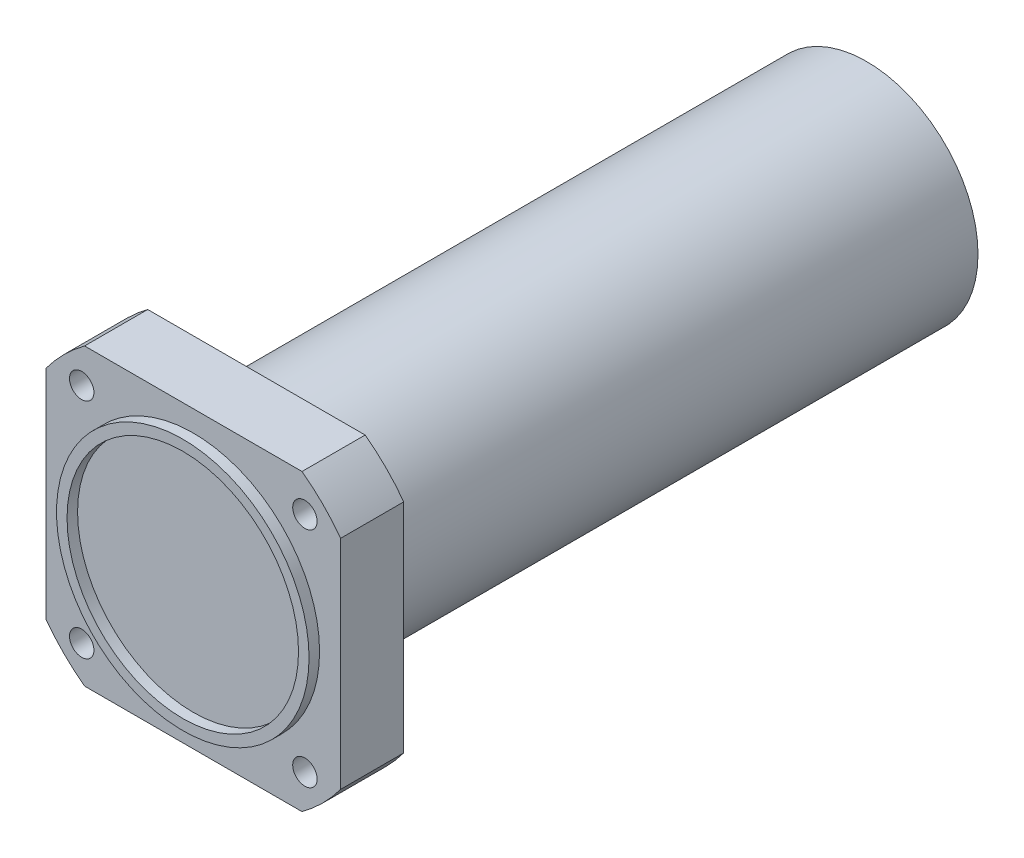
SolidWorks part; units mm, degrees
ref_plane "Спереди" through (0, 0, 0) normal (0, 0, 1) x (1, 0, 0)
ref_plane "Сверху" through (0, 0, 0) normal (0, 1, 0) x (1, 0, 0)
ref_plane "Справа" through (0, 0, 0) normal (1, 0, 0) x (0, 0, -1)
sketch "Эскиз2" plane through (0, 0, 0) normal (1, 0, 0) x (0, 0, -1)
  line L0 (-160, -35.0567) -> (-160, 34.9433)
  line L1 (-160, -35.0567) -> (-145, -35.0567)
  line L2 (-145, -35.0567) -> (-145, 34.9433)
  line L3 (-162.5, -30.0567) -> (-160, -30.0567)
  line L4 (0, -26.5) -> (0, 26.5)
  line L5 (0, 26.5) -> (-145, 26.5)
  line L6 (0, -26.5) -> (-145, -26.5)
  line L7 (-160, 34.9433) -> (-145, 34.9433)
  line L8 (-162.5, -30.0567) -> (-162.5, -27.5567)
  line L9 (-162.5, -27.5567) -> (-160, -27.5567)
  line L10 (-162.5, 29.9433) -> (-160, 29.9433)
  line L11 (-162.5, 29.9433) -> (-162.5, 27.4433)
  line L12 (-162.5, 27.4433) -> (-160, 27.4433)
  line L13 (-165.8901, -0.0567) -> (14.571, -0.0567) construction
revolve "Повернуть2" add sketch "Эскиз2" angle 360 about L13 region at (0, -28.8067, 161.25) region at (0, -13.2783, 72.5)
extrude "Бобышка-Вытянуть1" add sketch "Эскиз2<4>" along normal blind 35 and the other way blind 35 contours L1 L2 L7 L0
sketch "Эскиз2<4>" plane through (0, 0, 0) normal (1, 0, 0) x (0, 0, -1) same geometry as "Эскиз2"
sketch "Эскиз4" plane through (0, 0, 160) normal (0, 0, 1) x (1, 0, 0)
  line L0 (30.7591, -30.8158) -> (0, -0.0567)
  line L1 (0, -0.0567) -> (30.7591, 30.7025)
  line L2 (0, -0.0567) -> (-30.7591, -30.8158)
  line L3 (-30.7591, 30.7025) -> (0, -0.0567)
  circle A0 centre (0, -0.0567) radius 43.5
  circle A1 centre (0, -0.0567) radius 37.5
  point P9 (-26.5165, -26.5732)
  point P10 (26.5165, -26.5732)
  point P11 (26.5165, 26.4598)
  point P12 (-26.5165, 26.4598)
  line M4 (-35, -35.0567) -> (35, -35.0567)
  line M5 (35, -35.0567) -> (35, 34.9433)
  line M6 (35, 34.9433) -> (-35, 34.9433)
  line M7 (-35, 34.9433) -> (-35, -35.0567)
extrude "Вырез-Вытянуть1" cut sketch "Эскиз4" against normal through all contours A0 M7 M4 | A0 M4 M5 | A0 M5 M6 | A0 M6 M7 region at (32.0983, -32.155, 160) region at (-32.0983, -32.155, 160) region at (32.0983, 32.0416, 160) region at (-32.0983, 32.0416, 160)
hole_wizard "Диаметр отверстия Ø5.8 (5.8)1" positions "Трехмерный эскиз1" profile "Эскиз5" hole size "Ø5.8" standard "ГОСТ" end condition through all
sketch3d "Трехмерный эскиз1"
  point P0 (-26.5165, -26.5732, 160)
  point P3 (26.5165, -26.5732, 160)
  point P6 (26.5165, 26.4598, 160)
  point P9 (-26.5165, 26.4598, 160)
sketch "Эскиз5" plane through (-26.5165, -26.5732, 160) normal (1, 0, 0) x (0, -1, 0)
  line L0 (0, 0) -> (0, 160)
  line L1 (0, 160) -> (2.9, 160)
  line L2 (2.9, 160) -> (2.9, 0)
  line L5 (2.9, 0) -> (0, 0)
  line L11 (0, -6.35) -> (0, 107.95) construction
  dimension "Диаметр сквозного отверстия" = 5.8
  dimension "Глубина сквозного отверстия" = 160
